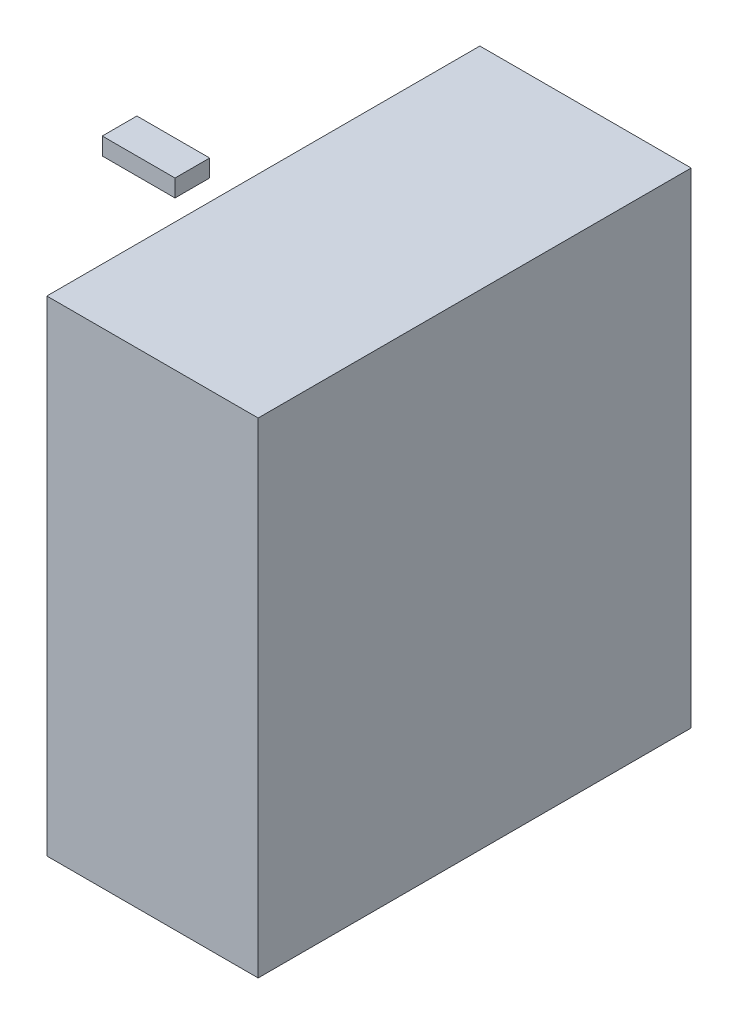
SolidWorks part; units mm, degrees
ref_plane "Front Plane" through (0, 0, 0) normal (0, 0, 1) x (1, 0, 0)
ref_plane "Top Plane" through (0, 0, 0) normal (0, 1, 0) x (1, 0, 0)
ref_plane "Right Plane" through (0, 0, 0) normal (1, 0, 0) x (0, 0, -1)
sketch "Sketch1" plane through (0, 0, 0) normal (0, 1, 0) x (1, 0, 0)
  line L7 (-2.1, -7.8) -> (0, -7.8)
  line L8 (-2.1, -7.8) -> (-2.1, -8.8)
  line L9 (-2.1, -8.8) -> (0, -8.8)
  line L10 (0, -7.8) -> (0, -8.8)
  line L11 (0, 0) -> (6.1, 0)
  line L12 (0, 0) -> (0, -12.5)
  line L13 (0, -12.5) -> (6.1, -12.5)
  line L14 (6.1, 0) -> (6.1, -12.5)
  point P0 (4.1, -6.5)
  point P10 (-2.1, -8.3)
  dimension "D1" = 2.1
  dimension "D2" = 1
  dimension "D3" = 6.5
  dimension "D4" = 1.8
  dimension "D5" = 6.1
  dimension "D6" = 12.5
  dimension "D7" = 2
extrude "Boss-Extrude1" add sketch "Sketch1" along normal blind 14 contours L14 L11 L12 L10 L13 region at (3.05, 0, 6.25)
extrude "Boss-Extrude2" add sketch "Sketch1<3>" against normal blind 0.5 from offset 0.6 contours L10 L7 L8 L9 region at (-1.05, 0, 8.3) offset against normal yes
sketch "Sketch1<3>" plane through (0, 0, 0) normal (0, 1, 0) x (1, 0, 0) same geometry as "Sketch1"
extrude "Boss-Extrude3" add sketch "Sketch1<4>" along normal blind 0.5 from offset 14.6 contours L10 L7 L8 L9 region at (-1.05, 0, 8.3)
sketch "Sketch1<4>" plane through (0, 0, 0) normal (0, 1, 0) x (1, 0, 0) same geometry as "Sketch1"
